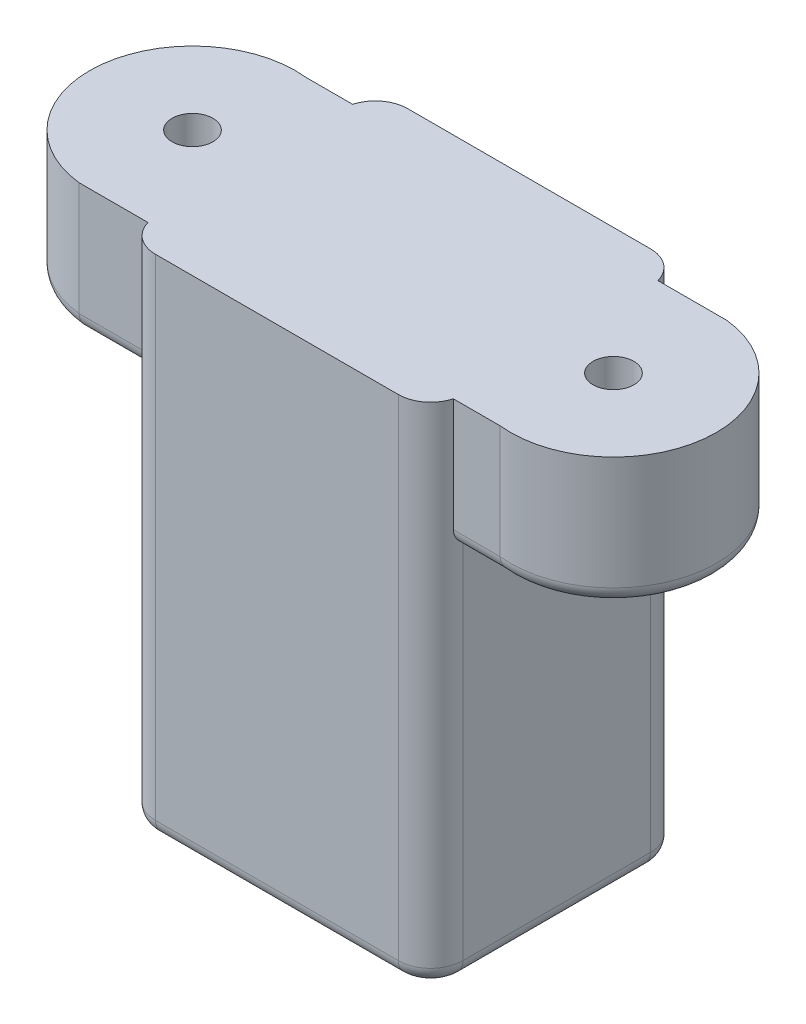
SolidWorks part; units mm, degrees
ref_plane "Front" through (0, 0, 0) normal (0, 0, 1) x (1, 0, 0)
ref_plane "Top" through (0, 0, 0) normal (0, 1, 0) x (1, 0, 0)
ref_plane "Right" through (0, 0, 0) normal (1, 0, 0) x (0, 0, -1)
sketch "Sketch1" plane through (0, 0, 0) normal (0, 1, 0) x (1, 0, 0)
  line L1 (7.824, -4.0132) -> (-8.686, -4.0132)
  line L3 (8.686, 4.0132) -> (-7.824, 4.0132)
  line L5 (7.824, -4.0132) -> (-7.824, 4.0132) construction
  line L6 (8.686, 4.0132) -> (-8.686, -4.0132) construction
  arc A0 (-7.824, 4.0132) -> (-8.686, -4.0132) centre (-8.255, 0) ccw
  arc A1 (8.686, 4.0132) -> (7.824, -4.0132) centre (8.255, 0) cw
  point P0 (0, 0)
  dimension "D1" = 8.0264
  dimension "D2" = 16.51
extrude "Boss-Extrude1" add sketch "Sketch1" along normal blind 5.08 contours L3 A0 L1 A1
ref_axis "Axis1" through (-8.255, 5.08, 0) along (0, -1, 0)
ref_axis "Axis2" through (8.255, 5.08, 0) along (0, -1, 0)
hole_wizard "M2x0.4 Tapped Hole1" positions "Sketch6" profile "Sketch7" tap size "M2x0.4" standard "ANSI Metric" end condition through all
sketch "Sketch6" plane through (0, 5.08, 0) normal (0, 1, 0) x (1, 0, 0)
  point P0 (-8.255, 0)
  point P2 (8.255, 0)
sketch "Sketch7" plane through (-8.255, 5.08, 0) normal (1, 0, 0) x (0, 0, 1)
  line L0 (0, 0) -> (0, 5.08)
  line L1 (0, 5.08) -> (0.8, 5.08)
  line L2 (0.8, 5.08) -> (0.8, 0)
  line L5 (0.8, 0) -> (0, 0)
  line L11 (0, -6.35) -> (0, 107.95) construction
  dimension "Thru Tap Drill Dia." = 1.6
  dimension "Thru Tap Drill Depth" = 5.08
cosmetic thread "Hole Thread1" parameters "D2"=2
cosmetic thread "Hole Thread2" parameters "D2"=2
sketch "Sketch8" plane through (0, 5.08, 0) normal (0, 1, 0) x (1, 0, 0)
  line L1 (6.0325, -4.9466) -> (-6.0325, -4.9466)
  line L2 (6.0325, -4.9466) -> (6.0325, 4.9467)
  line L3 (6.0325, 4.9467) -> (-6.0325, 4.9466)
  line L4 (-6.0325, -4.9466) -> (-6.0325, 4.9466)
  line L5 (6.0325, -4.9466) -> (-6.0325, 4.9466) construction
  line L6 (6.0325, 4.9467) -> (-6.0325, -4.9466) construction
  point P0 (0, 0)
  dimension "D1" = 12.065
  dimension "D2" = 9.8933
extrude "Boss-Extrude2" add sketch "Sketch8" against normal blind 19.8628
fillet "Fillet1" radius 1.27 4 edges at (-6.0325, -4.8514, 4.9466) (6.0325, -4.8514, 4.9466) (-6.0325, -4.8514, -4.9466) (6.0325, -4.8514, -4.9467)
fillet "Fillet2" radius 0.635 6 edges at (-7.3365, 0, 4.0132) (-12.2682, 0, -0.431) (-6.9055, 0, -4.0132) (7.3365, 0, -4.0132) (6.9055, 0, 4.0132) (12.2682, 0, 0.431)
fillet "Fillet3" radius 0.635 8 edges at (5.6605, -14.7828, 4.5747) (6.0325, -14.7828, 0) (5.6605, -14.7828, -4.5747) (0, -14.7828, -4.9467) (-5.6605, -14.7828, -4.5747) (-6.0325, -14.7828, 0) (-5.6605, -14.7828, 4.5747) (0, -14.7828, 4.9466)
